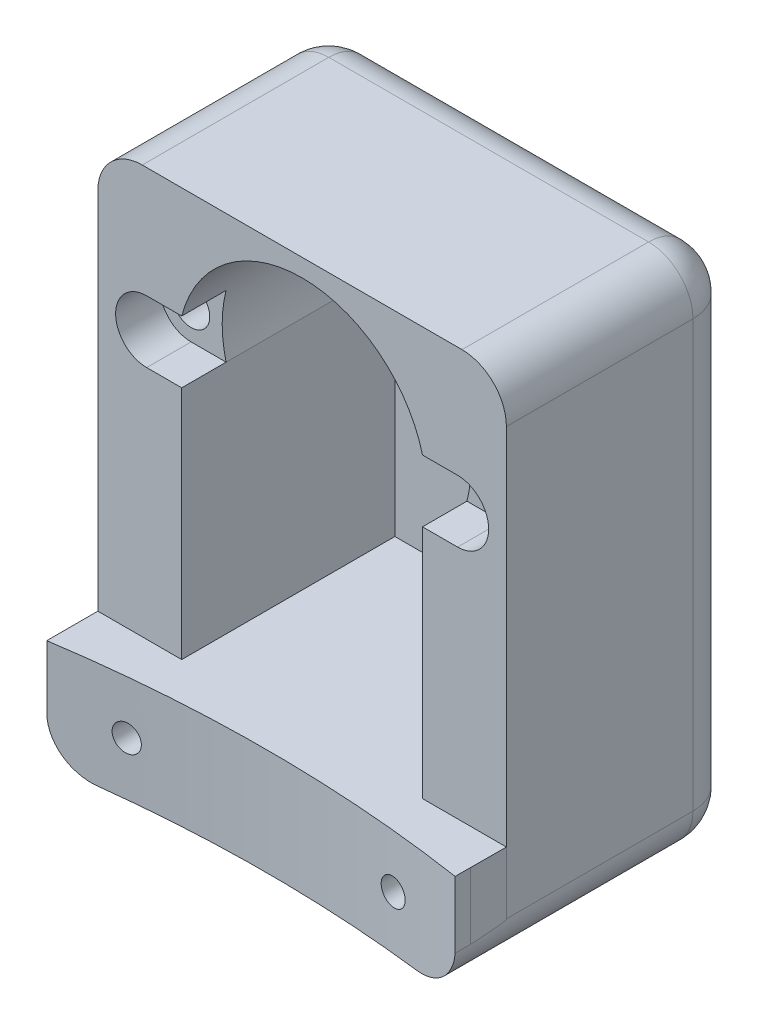
SolidWorks part; units mm, degrees
ref_plane "Plan de face" through (0, 0, 0) normal (0, 0, 1) x (1, 0, 0)
ref_plane "Plan de dessus" through (0, 0, 0) normal (0, 1, 0) x (1, 0, 0)
ref_plane "Plan de droite" through (0, 0, 0) normal (1, 0, 0) x (0, 0, -1)
sketch "Esquisse1" plane through (0, 0, 0) normal (0, 1, 0) x (0, 0, -1)
  line L0 (154, 24.2519) -> (154, -22.8929) construction
  line L1 (158, 23) -> (158, -23)
  line L2 (158, -23) -> (184, -23)
  line L4 (158, 23) -> (184, 23)
  line L5 (184, -23) -> (184, 23)
  dimension "D1" = 46
  dimension "D3" = 26
  dimension "D4" = 4
extrude "Boss.-Extru.1" add sketch "Esquisse1" along normal blind 10
extrude "Boss.-Extru.2" add sketch "Esquisse1<5>" against normal blind 48
sketch "Esquisse1<5>" plane through (0, 0, 0) normal (0, 1, 0) x (0, 0, -1) same geometry as "Esquisse1"
sketch "Esquisse2" plane through (0, 0, -158) normal (0, 0, 1) x (1, 0, 0)
  line L0 (-17.5, -2.5) -> (-13.5554, -2.5)
  line L1 (-17.5, -9.5) -> (-13.5554, -9.5)
  line L2 (17.5, -2.5) -> (13.5554, -2.5)
  line L3 (17.5, -9.5) -> (13.5554, -9.5)
  line L4 (-13.5554, -36) -> (13.5554, -36)
  line L5 (-13.5554, -9.5) -> (-13.5554, -36)
  line L6 (13.5554, -9.5) -> (13.5554, -36)
  line L7 (-23, 10) -> (-23, -48) construction
  line L9 (-23, 10) -> (23, 10) construction
  circle A0 centre (0, 2) radius 2.5
  circle A1 centre (0, -6) radius 14
  arc A2 (-17.5, -2.5) -> (-17.5, -9.5) centre (-17.5, -6) ccw
  arc A3 (17.5, -9.5) -> (17.5, -2.5) centre (17.5, -6) ccw
  circle A4 centre (-17.5, -6) radius 2.1
  circle A5 centre (17.5, -6) radius 2.1
  dimension "D1" = 5
  dimension "D2" = 28
  dimension "D6" = 7
  dimension "D7" = 7
  dimension "D8" = 4.2
  dimension "D9" = 4.2
  dimension "D3" = 8
  dimension "D4" = 17.5
  dimension "D5" = 17.5
  dimension "D10" = 30
  dimension "D11" = 23
  dimension "D12" = 16
  dimension "D13" = 38
extrude "Enlèv. mat.-Extru.1" cut sketch "Esquisse2" against normal blind 24 contours A1 A0 | A1 L5 L4 L6 | A0 region at (0, -6.2635, -158) region at (0, -26.4387, -158) region at (0, 2, -158)
extrude "Enlèv. mat.-Extru.2" cut sketch "Esquisse2<17>" against normal blind 5 contours L0 A2 L1 A1 A4 | L3 A3 L2 A1 A5 region at (-15.5277, -2.6022, -158) region at (15.5277, -2.6022, -158)
sketch "Esquisse2<17>" plane through (0, 0, -158) normal (0, 0, 1) x (1, 0, 0) same geometry as "Esquisse2"
extrude "Enlèv. mat.-Extru.3" cut sketch "Esquisse2<18>" against normal blind 14 contours A4 | A5 region at (-17.5, -6, -158) region at (17.5, -6, -158)
sketch "Esquisse2<18>" plane through (0, 0, -158) normal (0, 0, 1) x (1, 0, 0) same geometry as "Esquisse2"
sketch "Esquisse5" plane through (0, -48, 0) normal (0, -1, 0) x (1, 0, 0)
  line L0 (0, -177.7431) -> (0, -150.3257) construction
  line L2 (-23, -158) -> (-23, -154)
  line L4 (22.9757, -154) -> (23, -158)
  line L5 (-23, -154) -> (-23, -152.2498)
  line L6 (22.9757, -154) -> (22.9757, -152.2535)
  line L10 (-23, -184) -> (23, -184)
  line L11 (23, -184) -> (23, -158)
  line L12 (23, -158) -> (-23, -158)
  line L13 (-23, -158) -> (-23, -184)
  line L14 (-23, -184) -> (23, -184)
  line L15 (23, -184) -> (23, -158)
  line L17 (-23, -158) -> (-23, -184)
  arc A0 (-23, -152.2498) -> (22.9757, -152.2535) centre (0, -2) ccw
  dimension "D1" = 304
  dimension "D2" = 4
  dimension "D3" = 0
extrude "Boss.-Extru.7" add sketch "Esquisse5" against normal blind 12
fillet "Congé1" radius 5 3 edges at (23, 10, -171) (23, -19, -184) (0, 10, -184)
fillet "Congé2" radius 5 7 edges at (21.5355, -48, -182.5355) (-23, 8.5355, -182.5355) (-23, -48, -168.1249) (23, -48, -168.5) (-2.5, -48, -184) (-23, -21.5, -184) (-23, 10, -168.5)
sketch "Esquisse6" plane through (0, 0, 0) normal (0, 0, 1) x (1, 0, 0)
  line L0 (0, 10) -> (0, -49.3379) construction
  line L1 (-18, 10) -> (18, 10) construction
  line L2 (-18.6497, -42) -> (22.9794, -42) construction
  line L3 (-13.5554, -36) -> (13.5554, -36) construction
  circle A0 centre (-15, -42) radius 1.5
  circle A1 centre (15, -42) radius 1.5
  dimension "D1" = 3
  dimension "D2" = 3
  dimension "D3" = 15
  dimension "D4" = 15
  dimension "D5" = 6
extrude "Enlèv. mat.-Extru.4" cut sketch "Esquisse6" against normal blind 174
